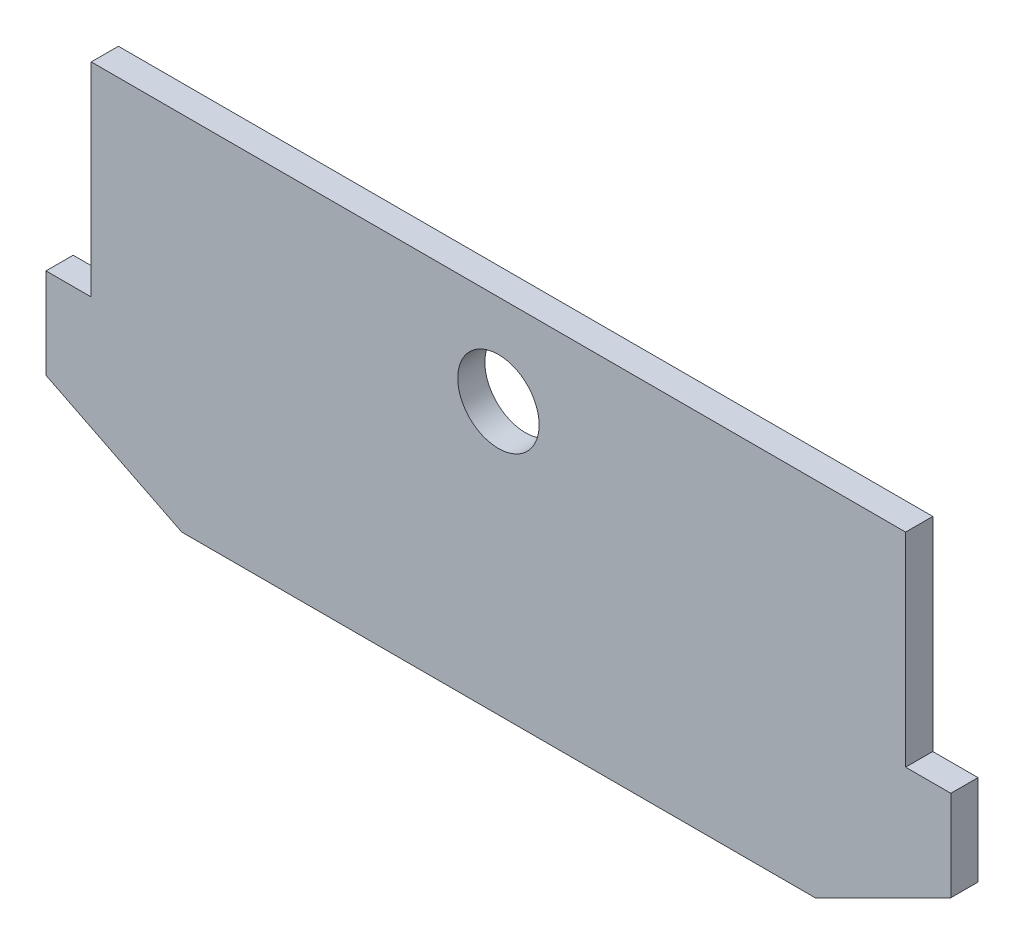
SolidWorks part; units mm, degrees
ref_plane "Front Plane" through (0, 0, 0) normal (0, 0, 1) x (1, 0, 0)
ref_plane "Top Plane" through (0, 0, 0) normal (0, 1, 0) x (1, 0, 0)
ref_plane "Right Plane" through (0, 0, 0) normal (1, 0, 0) x (0, 0, -1)
sketch "Sketch1" plane through (0, 0, 0) normal (0, 0, 1) x (1, 0, 0)
  line L1 (-90, 20) -> (90, 20)
  line L2 (-90, 20) -> (-90, -25)
  line L3 (-70, -60) -> (70, -60)
  line L4 (90, 20) -> (90, -25)
  line L5 (0, 20) -> (0, -60) construction
  line L6 (70, -60) -> (100, -45)
  line L7 (100, -45) -> (100, -25)
  line L8 (100, -25) -> (90, -25)
  line L9 (-100, -45) -> (-100, -25)
  line L10 (-70, -60) -> (-100, -45)
  line L11 (-100, -25) -> (-90, -25)
  circle A0 centre (0, 0) radius 9
  point P9 (0, 0)
  point P16 (0, 0)
  dimension "D1" = 180
  dimension "D3" = 18
  dimension "D2" = 20
  dimension "D4" = 80
  dimension "D5" = 200
  dimension "D6" = 45
  dimension "D7" = 20
  dimension "D8" = 140
extrude "Boss-Extrude1" add sketch "Sketch1" along normal blind 3 and the other way blind 3
